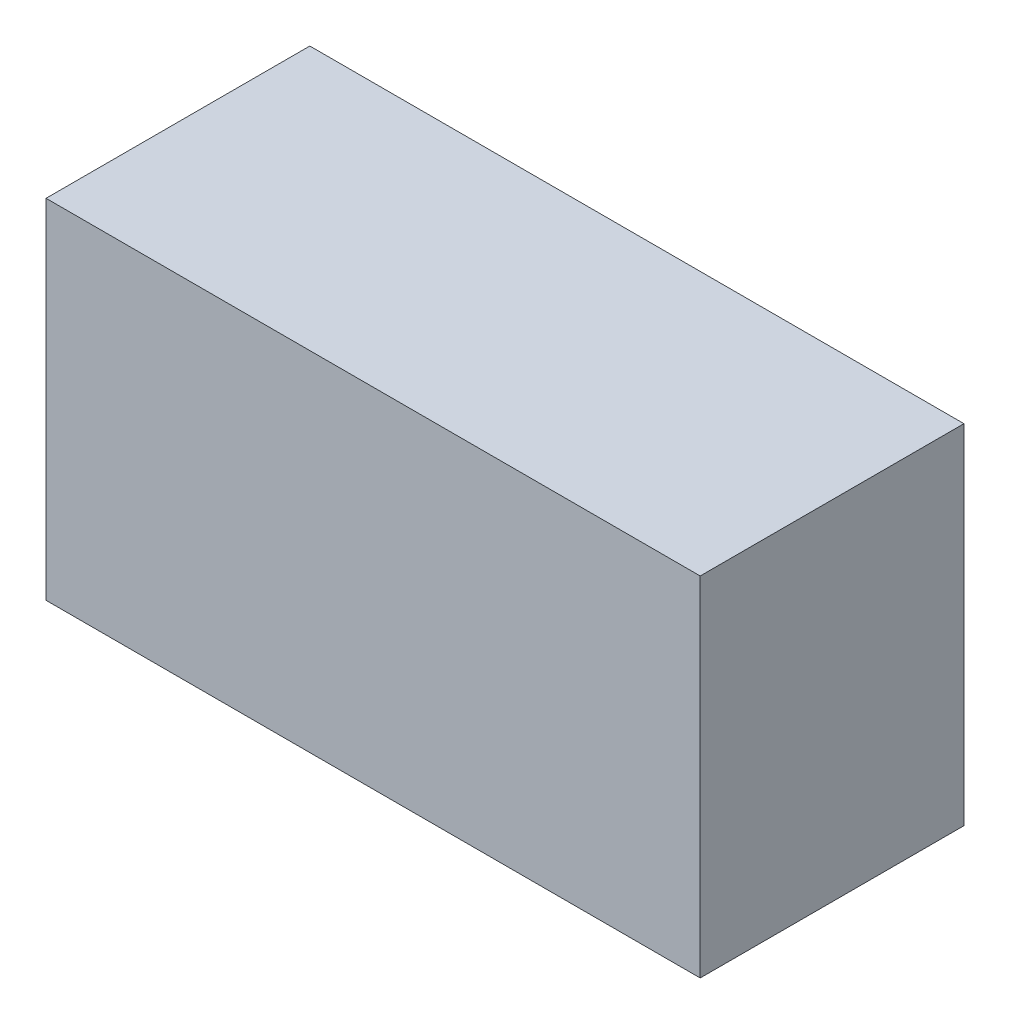
SolidWorks part; units mm, degrees
ref_plane "Front Plane" through (0, 0, 0) normal (0, 0, 1) x (1, 0, 0)
ref_plane "Top Plane" through (0, 0, 0) normal (0, 1, 0) x (1, 0, 0)
ref_plane "Right Plane" through (0, 0, 0) normal (1, 0, 0) x (0, 0, -1)
sketch "Sketch1" plane through (0, 0, 0) normal (0, 1, 0) x (1, 0, 0)
  line L1 (0, 25) -> (62, 25)
  line L2 (0, 25) -> (0, 0)
  line L3 (0, 0) -> (62, 0)
  line L4 (62, 25) -> (62, 0)
  dimension "D1" = 25
  dimension "D2" = 62
extrude "Boss-Extrude1" add sketch "Sketch1" along normal blind 33
